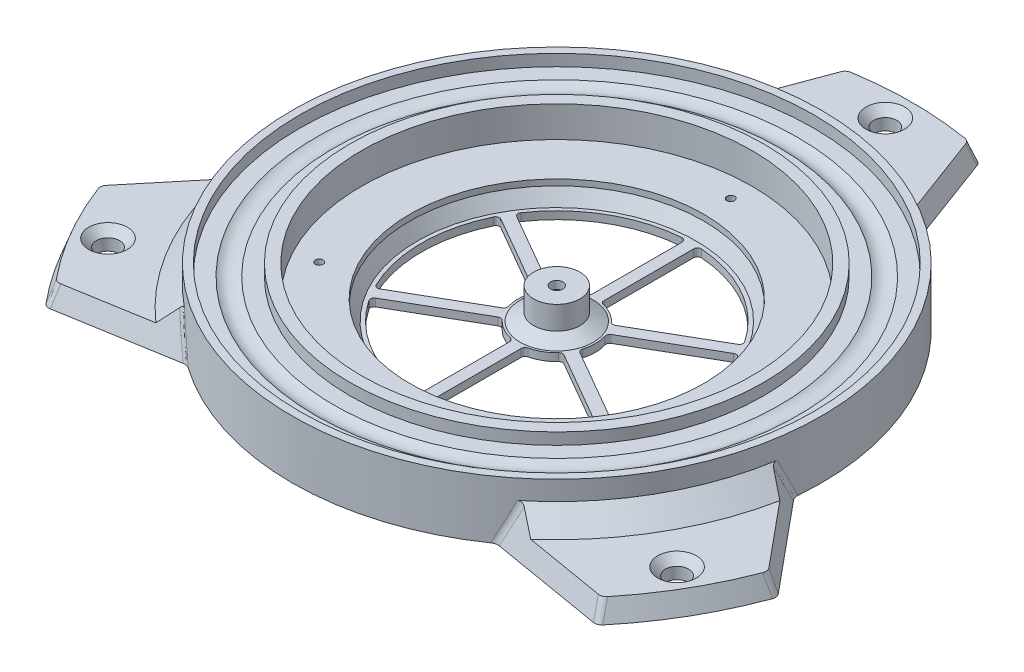
SolidWorks part; units mm, degrees
material "ABS"
ref_plane "Front Plane" through (0, 0, 0) normal (0, 0, 1) x (1, 0, 0)
ref_plane "Top Plane" through (0, 0, 0) normal (0, 1, 0) x (1, 0, 0)
ref_plane "Right Plane" through (0, 0, 0) normal (1, 0, 0) x (0, 0, -1)
sketch "Sketch1" plane through (0, 0, 0) normal (0, 0, 1) x (1, 0, 0)
  line L0 (0, 0) -> (0, 10)
  line L1 (0, 10) -> (6, 10)
  line L2 (6, 10) -> (6, 2)
  line L3 (6, 2) -> (38, 2)
  line L4 (38, 2) -> (38, 7)
  line L5 (38, 7) -> (50.5, 7)
  line L6 (50.5, 7) -> (50.5, 15)
  line L8 (68.5, 15) -> (68.5, 0)
  line L9 (68.5, 0) -> (0, 0)
  line L10 (68.5, 15) -> (66.5, 15)
  line L11 (66.5, 15) -> (66.5, 12)
  line L12 (66.5, 12) -> (62.3516, 12)
  line L13 (50.5, 15) -> (53.5, 15)
  line L14 (53.5, 15) -> (53.5, 12)
  line L15 (53.5, 12) -> (57.6484, 12)
  arc A0 (57.6484, 12) -> (62.3516, 12) centre (60, 15.6) ccw
  dimension "D3" = 4.3
  dimension "D1" = 50.5
  dimension "D2" = 8
  dimension "D4" = 60
  dimension "D5" = 6.5
  dimension "D6" = 6
  dimension "D7" = 2
  dimension "D8" = 10
  dimension "D9" = 5
  dimension "D10" = 2
  dimension "D11" = 38
  dimension "D12" = 6.5
  dimension "D13" = 3
  dimension "D14" = 0.6
revolve "Revolve1" add sketch "Sketch1" angle 360 about L0
sketch "Sketch2" plane through (0, 0, 0) normal (0, 1, 0) x (1, 0, 0)
  line L0 (0, 0) -> (0, 42) construction
  line L1 (0, 0) -> (-36.3731, 21) construction
  line L4 (-28.6152, 18.253) -> (-8.527, 6.6551)
  line L5 (-1.5, 33.908) -> (-1.5, 10.7121)
  arc A0 (-2.5735, 34.9053) -> (-28.9421, 19.6814) centre (0, 0) ccw
  arc A1 (-7.2973, 6.8374) -> (-2.2727, 9.7383) centre (0, 0) cw
  arc A6 (-2.2727, 9.7383) -> (-1.5, 10.7121) centre (-2.5, 10.7121) ccw
  arc A7 (-7.2973, 6.8374) -> (-8.527, 6.6551) centre (-8.027, 7.5211) cw
  arc A8 (-1.5, 33.908) -> (-2.5735, 34.9053) centre (-2.5, 33.908) ccw
  arc A9 (-28.6152, 18.253) -> (-28.9421, 19.6814) centre (-28.1152, 19.119) cw
  point P8 (0, 8)
  point P11 (-6.9282, 4)
  dimension "D2" = 35
  dimension "D3" = 10
  dimension "D4" = 1.5
  dimension "D5" = 3
  dimension "D6" = 1
  dimension "D1" = 60
extrude "Cut-Extrude1" cut sketch "Sketch2" along normal through all
pattern_circular "CirPattern1" count 6 over 360 about axis through (0, 10, 0) along (0, -1, 0) of "Cut-Extrude1"
sketch "Sketch3" plane through (0, 0, 0) normal (0, 1, 0) x (1, 0, 0)
  line L0 (0, 0) -> (0, 95) construction
  line L1 (32, 55.608) -> (18, 93.2792)
  line L2 (-32, 55.608) -> (-18, 93.2792)
  arc A0 (-18, 93.2792) -> (18, 93.2792) centre (0, 0) cw
  arc A1 (-32, 55.608) -> (32, 55.608) centre (0, 0) cw
  circle A3 centre (0, 85) radius 3
  dimension "D1" = 95
  dimension "D4" = 6
  dimension "D2" = 32
  dimension "D3" = 18
  dimension "D5" = 85
extrude "Boss-Extrude1" add sketch "Sketch3" along normal blind 5
chamfer "Chamfer1" distance 3 angle 70 3 edges at (-23.8659, 5, -77.4952) (0, 5, -95) (23.8659, 5, -77.4952) first distance on face at (0, 5, -79.6226)
chamfer "Chamfer2" distance 2 angle 45 1 edges at (0, 5, -82)
chamfer "Chamfer4" distance 5 angle 45 1 edges at (0, 5, -68.5)
fillet "Fillet1" radius 2 4 edges at (25.936, 4.9169, -63.4001) (-25.936, 4.9169, -63.4001)
pattern_circular "CirPattern2" count 3 over 360 about axis through (0, 0, 0) along (0, -1, 0) of "Chamfer2", "Boss-Extrude1", "Chamfer1", "Chamfer4", "Fillet1" reverse direction yes
sketch "Sketch4" plane through (0, 10, 0) normal (0, 1, 0) x (1, 0, 0)
  circle A0 centre (0, 0) radius 1.6
  dimension "D1" = 3.2
extrude "Cut-Extrude2" cut sketch "Sketch4" against normal through all
sketch "Sketch5" plane through (0, 0, 0) normal (0, -1, 0) x (1, 0, 0)
  circle A0 centre (0, 0) radius 2.025
  dimension "D1" = 4.05
extrude "Cut-Extrude3" cut sketch "Sketch5" against normal blind 8
chamfer "Chamfer5" distance 2 angle 60 2 edges at (0, 2, -38) (0, 2, -6) first distance on face at (0, 2, -6) first distance on face at (0, 10, -6)
sketch "Sketch6" plane through (0, 7, 0) normal (0, 1, 0) x (1, 0, 0)
  circle A0 centre (0, 45) radius 1
  dimension "D2" = 2
  dimension "D1" = 45
extrude "Cut-Extrude4" cut sketch "Sketch6" against normal blind 5
pattern_circular "CirPattern3" count 3 over 360 about axis through (0, 5.4641, 0) along (0, -1, 0) of "Cut-Extrude4"
